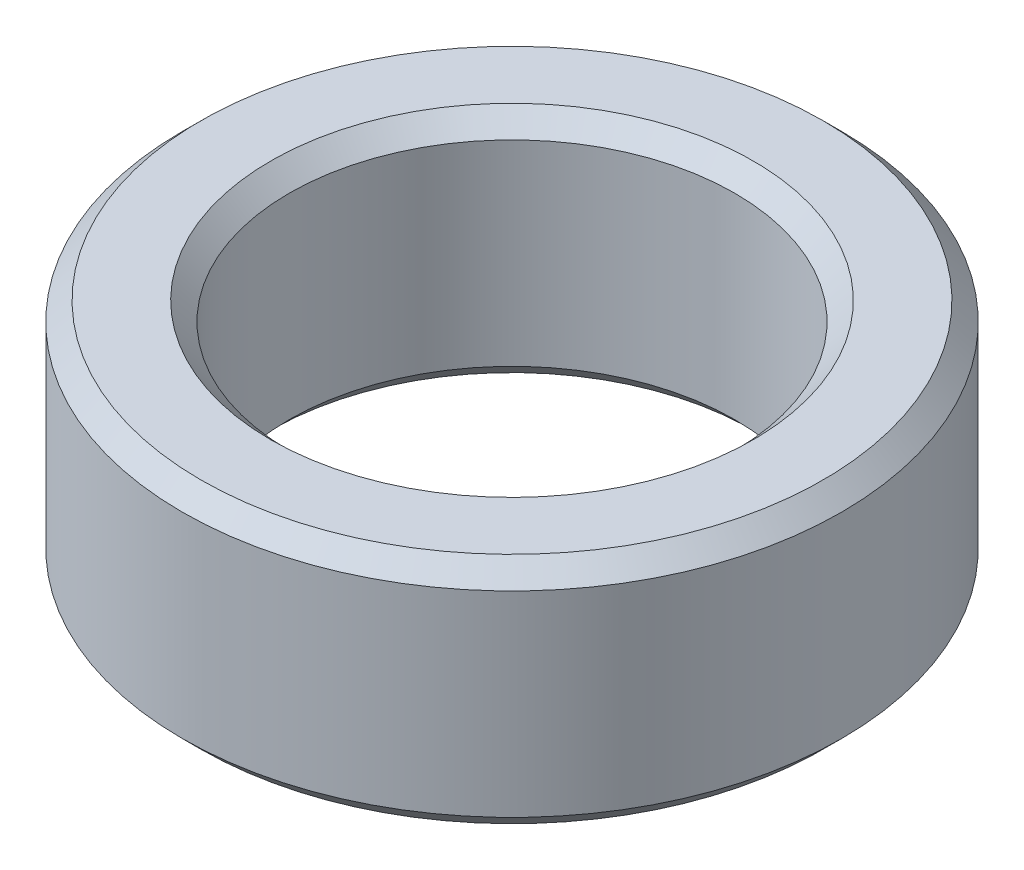
SolidWorks part; units mm, degrees
ref_plane "Front Plane" through (0, 0, 0) normal (0, 0, 1) x (1, 0, 0)
ref_plane "Top Plane" through (0, 0, 0) normal (0, 1, 0) x (1, 0, 0)
ref_plane "Right Plane" through (0, 0, 0) normal (1, 0, 0) x (0, 0, -1)
sketch "Sketch1" plane through (0, 0, 0) normal (0, 1, 0) x (1, 0, 0)
  circle A0 centre (0, 0) radius 12.5
  dimension "SLEEVE_OD" = 25
extrude "Boss-Extrude1" add sketch "Sketch1" along normal blind 8.8434
sketch "Sketch2" plane through (0, 0, 0) normal (0, 1, 0) x (1, 0, 0)
  circle A0 centre (0, 0) radius 8.4467
  dimension "BORE_D" = 16.8934
extrude "Cut-Extrude1" cut sketch "Sketch2" along normal through all
chamfer "Chamfer1" distance 0.7045 angle 45 4 edges at (0, 8.8434, 8.4467) (0, 0, 8.4467) (0, 0, 12.5) (0, 8.8434, 12.5)
